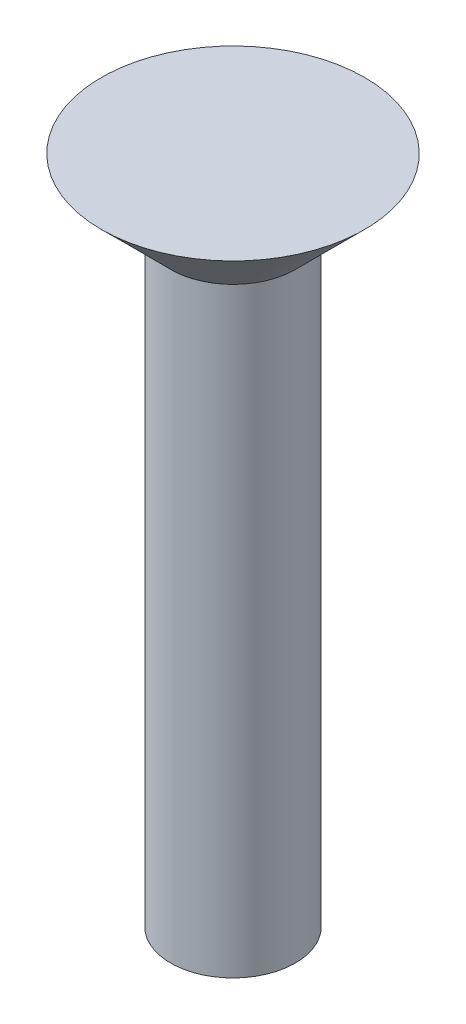
SolidWorks part; units mm, degrees
ref_plane "Front Plane" through (0, 0, 0) normal (0, 0, 1) x (1, 0, 0)
ref_plane "Top Plane" through (0, 0, 0) normal (0, 1, 0) x (1, 0, 0)
ref_plane "Right Plane" through (0, 0, 0) normal (1, 0, 0) x (0, 0, -1)
other "Default"
sketch "Threads" plane through (0, 0, 0) normal (0, 0, 1) x (1, 0, 0)
  line L0 (0, -6.5) -> (0, 6.5)
  line L1 (0, 6.5) -> (1.35, 6.5)
  line L2 (1.35, 6.5) -> (1.35, -6.5)
  line L3 (1.35, -6.5) -> (0, -6.5)
  line L4 (0, -5.7066) -> (0, 6.3425) construction
  dimension "Length" = 13
  dimension "Diameter" = 2.7
revolve "Revolve1" add sketch "Threads" angle 360 about L4
ref_plane "Head Top" through (0, 8, 0) normal (0, 1, 0) x (1, 0, 0)
sketch "Head" plane through (0, 8, 0) normal (0, 1, 0) x (1, 0, 0)
  circle A0 centre (0, 0) radius 2.85
  dimension "Diameter" = 5.7
sketch "Sketch5" plane through (0, 0, 0) normal (0, 0, 1) x (1, 0, 0)
  line L0 (2.85, 8) -> (-2.85, 8) construction
  line L1 (2.85, 8) -> (-2.85, 8) construction
  line L2 (0, -1.1215) -> (0, 5.6187) construction
  line L3 (0, 8) -> (0, 6.5)
  line L4 (0, 6.5) -> (1.35, 6.5)
  line L5 (1.35, 6.5) -> (2.85, 8)
  line L6 (2.85, 8) -> (0, 8)
revolve "Flat" add sketch "Sketch5" angle 360 about L2
